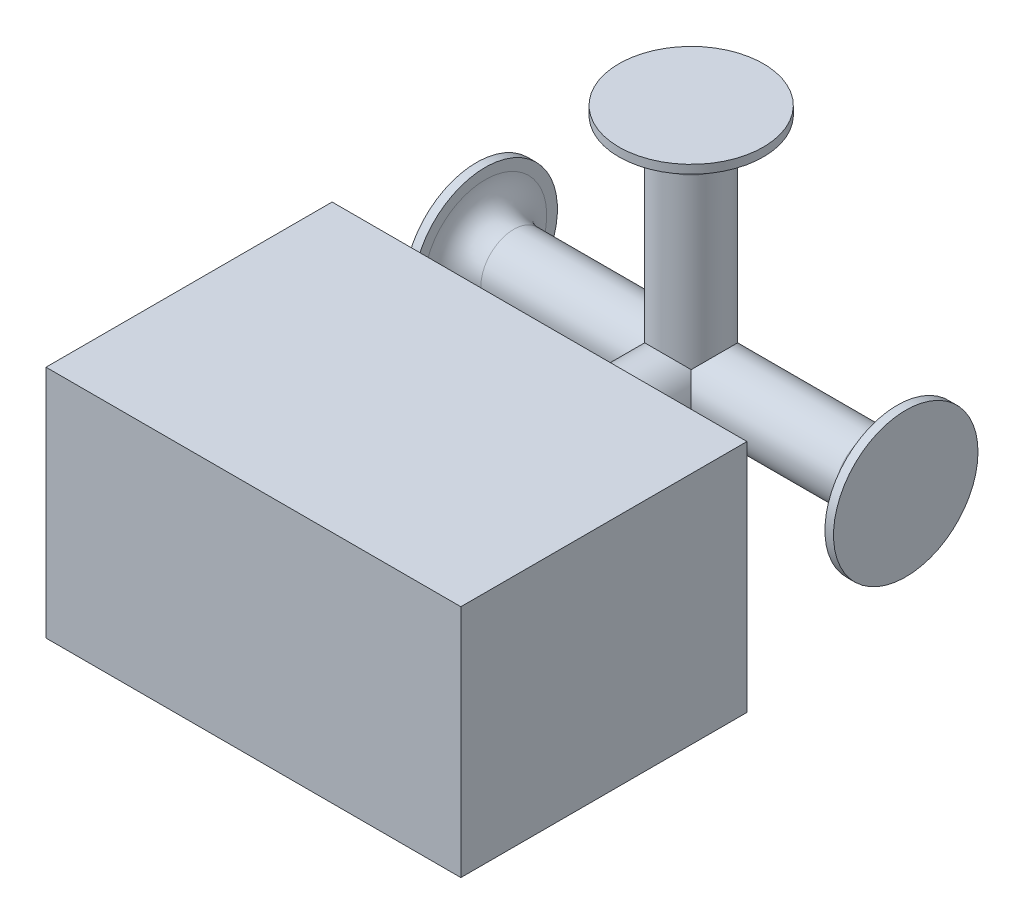
SolidWorks part; units mm, degrees
ref_plane "정면" through (0, 0, 0) normal (0, 0, 1) x (1, 0, 0)
ref_plane "윗면" through (0, 0, 0) normal (0, 1, 0) x (1, 0, 0)
ref_plane "우측면" through (0, 0, 0) normal (1, 0, 0) x (0, 0, -1)
sketch "스케치2" plane through (0, 0, 0) normal (0, 1, 0) x (1, 0, 0)
  circle A0 centre (0, 0) radius 25.25
  dimension "D1" = 50.5
extrude "보스-돌출1" add sketch "스케치2" against normal blind 3 contours A0
sketch "스케치3" plane through (0, -3, 0) normal (0, -1, 0) x (1, 0, 0)
  circle A0 centre (0, 0) radius 11.5
  dimension "D1" = 23
extrude "보스-돌출2" add sketch "스케치3" along normal blind 77
sketch "스케치4" plane through (0, 0, 0) normal (1, 0, 0) x (0, 0, -1)
  line L0 (-11.5, -80) -> (11.5, -80) construction
  circle A0 centre (0, -80) radius 11.5
  dimension "D1" = 23
extrude "보스-돌출3" add sketch "스케치4" along normal mid plane 144
sketch "스케치5" plane through (72, 0, 0) normal (1, 0, 0) x (0, 0, -1)
  circle A0 centre (0, -80) radius 25.25
  dimension "D1" = 50.5
extrude "보스-돌출4" add sketch "스케치5" along normal blind 3
sketch "스케치6" plane through (-72, 0, 0) normal (-1, 0, 0) x (0, 0, 1)
  circle A0 centre (0, -80) radius 25.25
  dimension "D1" = 50.5
extrude "보스-돌출5" add sketch "스케치6" along normal blind 3
fillet "필렛1" radius 10 3 edges at (-72, -80, -11.5) (0, -3, -11.5) (72, -80, -11.5)
sketch "스케치7" plane through (0, 0, 0) normal (0, 0, 1) x (1, 0, 0)
  circle A0 centre (0, -80) radius 11.5
  point P2 (0, 0)
  point P4 (-31.2906, -48.7094)
  dimension "D1" = 23
  dimension "D2" = 80
extrude "보스-돌출6" add sketch "스케치7" along normal blind 53 contours A0
ref_axis "기준축1" through (62, -80, 0) along (-1, 0, 0)
ref_plane "평면1" through (0, -80, 0) normal (0, 1, 0) x (1, 0, 0)
sketch "스케치8" plane through (0, -80, 0) normal (0, 1, 0) x (1, 0, 0)
  line L0 (-11.5, -53) -> (11.5, -53) construction
  line L1 (-72.5, -153) -> (72.5, -153)
  line L2 (-72.5, -153) -> (-72.5, -53)
  line L3 (-72.5, -53) -> (72.5, -53)
  line L4 (72.5, -153) -> (72.5, -53)
  line L5 (-72.5, -153) -> (72.5, -53) construction
  line L6 (-72.5, -53) -> (72.5, -153) construction
  point P0 (0, -103)
  point P7 (0, 0)
  dimension "D1" = 153
  dimension "D2" = 145
extrude "보스-돌출7" add sketch "스케치8" along normal mid plane 82
